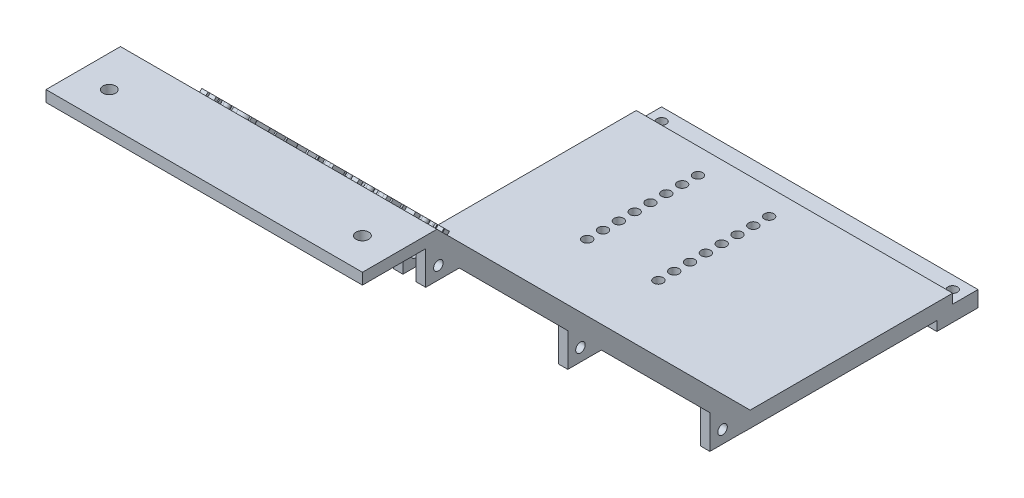
SolidWorks part; units mm, degrees
ref_plane "Front Plane" through (0, 0, 0) normal (0, 0, 1) x (1, 0, 0)
ref_plane "Top Plane" through (0, 0, 0) normal (0, 1, 0) x (1, 0, 0)
ref_plane "Right Plane" through (0, 0, 0) normal (1, 0, 0) x (0, 0, -1)
sketch "Sketch4" plane through (0, 0, 0) normal (1, 0, 0) x (0, 0, -1)
  line L0 (0, 0) -> (-8, 0)
  line L1 (-8, 0) -> (-8, 3)
  line L2 (-8, 3) -> (-72, 3)
  line L3 (-72, 3) -> (-170.9949, 101.9949)
  dimension "D1" = 8
  dimension "D2" = 3
  dimension "D3" = 64
  dimension "D4" = 135
  dimension "D5" = 140
extrude "Extrude-Thin2" add sketch "Sketch4" along normal blind 100 thin thin type one direction reverse wall 5
sketch "Sketch5" plane through (0, 3, 0) normal (0, 1, 0) x (1, 0, 0)
  line L1 (100, -8) -> (100, -72) construction
  line L2 (100, -8) -> (0, -8) construction
  circle A0 centre (50, -16) radius 1.5
  dimension "D2" = 3
  dimension "D1" = 50
  dimension "D3" = 8
extrude "Cut-Extrude1" cut sketch "Sketch5" against normal up to next
pattern_linear "LPattern1" count 8 spacing 5 along (0, 0, 1) count 2 spacing 22.5 along (-1, 0, 0) of "Cut-Extrude1"
sketch "Sketch7" plane through (100, 0, 0) normal (1, 0, 0) x (0, 0, -1)
  line L0 (-170.9949, 101.9949) -> (-174.5305, 101.9949)
  line L1 (-174.5305, 101.9949) -> (-174.5305, 98.4594)
  line L2 (-174.5305, 98.4594) -> (-170.9949, 101.9949)
extrude "Boss-Extrude1" add sketch "Sketch7" against normal up to surface (100 mm away) up to face at (0, 19.2454, 53.3597)
sketch "Sketch8" plane through (0, 0, 174.5305) normal (0, 0, 1) x (1, 0, 0)
  line L1 (0, 101.9949) -> (100, 101.9949)
  line L2 (0, 101.9949) -> (0, 98.4594)
  line L3 (0, 98.4594) -> (100, 98.4594)
  line L4 (100, 101.9949) -> (100, 98.4594)
extrude "Boss-Extrude2" add sketch "Sketch8" along normal blind 20
sketch "Sketch9" plane through (0, 101.9949, 0) normal (0, 1, 0) x (1, 0, 0)
  line L0 (100, -170.9949) -> (100, -194.5305) construction
  line L1 (100, -194.5305) -> (0, -194.5305) construction
  line L2 (0, -170.9949) -> (0, -194.5305) construction
  circle A0 centre (90, -184.5305) radius 2
  circle A1 centre (10, -184.5305) radius 2
  dimension "D1" = 4
  dimension "D2" = 4
  dimension "D3" = 10
  dimension "D4" = 10
  dimension "D5" = 10
  dimension "D6" = 10
extrude "Cut-Extrude2" cut sketch "Sketch9" against normal up to next
sketch "Sketch10" plane through (0, 0, 0) normal (0, 1, 0) x (1, 0, 0)
  line L0 (100, 0) -> (0, 0) construction
  line L1 (100, 0) -> (100, -8) construction
  line L2 (0, 0) -> (0, -8) construction
  circle A0 centre (4, -4) radius 1.5
  circle A1 centre (96, -4) radius 1.5
  dimension "D1" = 3
  dimension "D2" = 3
  dimension "D3" = 4
  dimension "D4" = 4
  dimension "D5" = 4
extrude "Cut-Extrude3" cut sketch "Sketch10" against normal up to next
sketch "Sketch11" plane through (100, 0, 0) normal (1, 0, 0) x (0, 0, -1)
  line L0 (-174.5305, 98.4594) -> (-174.5305, 87.8528)
  line L1 (-174.5305, 87.8528) -> (-163.9239, 87.8528)
  line L2 (-74.0711, -2) -> (-174.5305, 98.4594) construction
  line L3 (-174.5305, 98.4594) -> (-163.9239, 87.8528)
  dimension "D1" = 15
extrude "Boss-Extrude3" add sketch "Sketch11" against normal blind 3
sketch "Sketch12" plane through (100, 0, 0) normal (1, 0, 0) x (0, 0, -1)
  line L0 (-174.5305, 98.4594) -> (-174.5305, 87.8528) construction
  line L1 (-174.5305, 87.8528) -> (-163.9239, 87.8528) construction
  circle A0 centre (-170.5305, 91.8528) radius 1.5
  dimension "D1" = 3
  dimension "D2" = 4
  dimension "D3" = 4
extrude "Cut-Extrude4" cut sketch "Sketch12" against normal up to next
pattern_linear "LPattern2" count 3 spacing 63.5 along (0, -0.7071, -0.7071) count 2 spacing 97 along (-1, 0, 0) of "Boss-Extrude3", "Cut-Extrude4"
sketch "Sketch13" plane through (0, -2, 0) normal (0, -1, 0) x (1, 0, 0)
  line L0 (0, 13) -> (0, 74.0711) construction
  line L1 (0, 48.535) -> (3, 48.535)
  line L2 (0, 48.535) -> (0, 38.535)
  line L3 (0, 38.535) -> (3, 38.535)
  line L4 (3, 48.535) -> (3, 38.535)
  dimension "D1" = 3
  dimension "D2" = 10
  dimension "D3" = 25.535
extrude "Boss-Extrude4" add sketch "Sketch13" along normal blind 10
sketch "Sketch14" plane through (0, 0, 0) normal (-1, 0, 0) x (0, 0, 1)
  line L0 (38.535, -12) -> (38.535, -2) construction
  line L1 (48.535, -12) -> (38.535, -12) construction
  circle A0 centre (43.535, -7) radius 1.5
  dimension "D1" = 3
  dimension "D2" = 5
  dimension "D3" = 5
extrude "Cut-Extrude5" cut sketch "Sketch14" against normal up to next
sketch "Sketch15" plane through (0, -34.5, 34.5) normal (0, 0.7071, -0.7071) x (1, 0, 0)
  line L0 (100, -53.033) -> (100, -193.033) construction
  line L1 (100, -193.033) -> (0, -193.033) construction
  circle A0 centre (84, -176.233) radius 3.4
  circle A1 centre (84, -161.233) radius 3.4
  circle A2 centre (84, -146.233) radius 3.4
  circle A5 centre (84, -131.233) radius 3.4
  circle A6 centre (84, -116.233) radius 3.4
  circle A7 centre (84, -101.233) radius 3.4
  circle A8 centre (84, -86.233) radius 3.4
  dimension "D1" = 6.8
  dimension "D2" = 6.8
  dimension "D3" = 6.8
  dimension "D8" = 6.8
  dimension "D9" = 6.8
  dimension "D10" = 6.8
  dimension "D11" = 6.8
  dimension "D4" = 16
  dimension "D5" = 16.8
  dimension "D6" = 15
  dimension "D7" = 15
  dimension "D12" = 15
  dimension "D13" = 15
  dimension "D14" = 15
  dimension "D15" = 15
extrude "Cut-Extrude6" cut sketch "Sketch15" against normal up to next
sketch "Sketch16" plane through (0, -34.5, 34.5) normal (0, 0.7071, -0.7071) x (1, 0, 0)
  circle A0 centre (59, -161.233) radius 3.4
  circle A1 centre (44, -161.233) radius 3.4
  circle A2 centre (29, -161.233) radius 3.4
  circle A3 centre (14, -161.233) radius 3.4
  circle A5 centre (84, -161.233) radius 3.4 construction
  circle A6 centre (66.5, -146.233) radius 3.4
  circle A7 centre (51.5, -146.233) radius 3.4
  circle A8 centre (36.5, -146.233) radius 3.4
  circle A9 centre (21.5, -146.233) radius 3.4
  circle A10 centre (6.5, -146.233) radius 3.4
  circle A12 centre (51.5, -131.233) radius 3.4
  circle A13 centre (36.5, -131.233) radius 3.4
  circle A14 centre (21.5, -131.233) radius 3.4
  dimension "D1" = 6.8
  dimension "D2" = 15
  dimension "D3" = 15
  dimension "D7" = 6.8
  dimension "D14" = 6.8
  dimension "D4" = 15
  dimension "D5" = 0
  dimension "D6" = 25
  dimension "D8" = 15
  dimension "D9" = 15
  dimension "D10" = 15
  dimension "D11" = 15
  dimension "D12" = 7.5
  dimension "D13" = 15
  dimension "D15" = 15
  dimension "D16" = 15
  dimension "D17" = 15
extrude "Cut-Extrude7" cut sketch "Sketch16" against normal up to next
sketch "Sketch17" plane through (0, -34.5, 34.5) normal (0, 0.7071, -0.7071) x (1, 0, 0)
  circle A0 centre (51.5, -111.233) radius 3.4
  circle A1 centre (36.5, -106.233) radius 3.4
  circle A2 centre (21.5, -111.233) radius 3.4
  circle A3 centre (36.5, -131.233) radius 3.4 construction
  circle A4 centre (84, -116.233) radius 3.4 construction
  dimension "D1" = 6.8
  dimension "D4" = 5
  dimension "D2" = 15
  dimension "D3" = 15
  dimension "D5" = 0
  dimension "D6" = 5
extrude "Cut-Extrude8" cut sketch "Sketch17" against normal up to next
pattern_linear "LPattern3" count 4 spacing 15 along (0, -0.7071, -0.7071) of "Cut-Extrude8"
ref_plane "Plane1" through (0, -34.5, 34.5) normal (0, 0.7071, -0.7071) x (-1, 0, 0)
sketch "Sketch19" plane through (0, -34.5, 34.5) normal (0, 0.7071, -0.7071) x (-1, 0, 0)
  circle A0 centre (-84, 176.233) radius 3.4 construction
  text T0 "SENDS" font "Century Gothic" height 5
  dimension "D1" = 10
  dimension "D2" = 8
extrude "Boss-Extrude5" add sketch "Sketch19" along normal blind 1
sketch "Sketch21" plane through (0, -34.5, 34.5) normal (0, 0.7071, -0.7071) x (-1, 0, 0)
  circle A0 centre (-59, 161.233) radius 3.4 construction
  circle A1 centre (-44, 161.233) radius 3.4 construction
  circle A2 centre (-29, 161.233) radius 3.4 construction
  circle A3 centre (-14, 161.233) radius 3.4 construction
  circle A4 centre (-36.5, 146.233) radius 3.4 construction
  circle A5 centre (-66.5, 146.233) radius 3.4 construction
  circle A6 centre (-51.5, 146.233) radius 3.4 construction
  circle A7 centre (-21.5, 146.233) radius 3.4 construction
  circle A8 centre (-6.5, 146.233) radius 3.4 construction
  text T0 "DYANMICS\r\n" font "Century Gothic" height 5
  text T1 "THRESH"
  text T2 "ATK"
  text T3 "RLS"
  text T4 "KNEE"
  text T5 "THRESH"
  text T6 "ATK"
  text T7 "RLS"
  text T8 "KNEE"
  text T9 "RATIO" font "Century Gothic" height 3
  point P5 (0, 0)
  point P9 (0, 0)
  point P15 (0, 0)
  point P31 (0, 0)
  dimension "D1" = 8
  dimension "D2" = 4.25
  dimension "D3" = 4
  dimension "D4" = 6
  dimension "D5" = 20
  dimension "D6" = 8
  dimension "D7" = 5
  dimension "D8" = 5
  dimension "D9" = 4.25
  dimension "D10" = 4
  dimension "D11" = 6
  dimension "D12" = 6
extrude "Boss-Extrude6" add sketch "Sketch21" along normal blind 1
